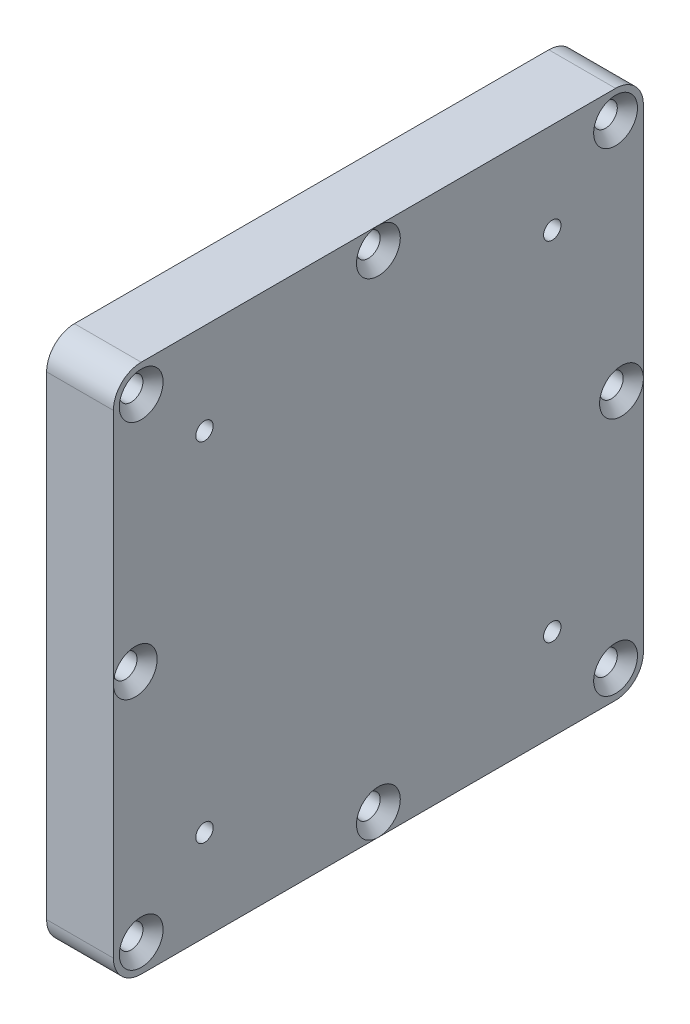
SolidWorks part; units mm, degrees
ref_plane "Front Plane" through (0, 0, 0) normal (0, 0, 1) x (1, 0, 0)
ref_plane "Top Plane" through (0, 0, 0) normal (0, 1, 0) x (1, 0, 0)
ref_plane "Right Plane" through (0, 0, 0) normal (1, 0, 0) x (0, 0, -1)
sketch "Sketch2" plane through (0, 0, 0) normal (1, 0, 0) x (0, 0, -1)
  line L1 (-34.1, -38.1) -> (34.1, -38.1)
  line L2 (-38.1, -34.1) -> (-38.1, 34.1)
  line L3 (-34.1, 38.1) -> (34.1, 38.1)
  line L4 (38.1, -34.1) -> (38.1, 34.1)
  line L5 (-38.1, -38.1) -> (38.1, 38.1) construction
  line L6 (-38.1, 38.1) -> (38.1, -38.1) construction
  arc A0 (-34.1, -38.1) -> (-38.1, -34.1) centre (-34.1, -34.1) cw
  arc A1 (34.1, -38.1) -> (38.1, -34.1) centre (34.1, -34.1) ccw
  arc A2 (34.1, 38.1) -> (38.1, 34.1) centre (34.1, 34.1) cw
  arc A3 (-38.1, 34.1) -> (-34.1, 38.1) centre (-34.1, 34.1) cw
  point P0 (0, 0)
  dimension "D3" = 4
  dimension "D1" = 76.2
  dimension "D2" = 76.2
extrude "Boss-Extrude1" add sketch "Sketch2" along normal blind 9.6
sketch "Sketch21" plane through (9.6, 0, 0) normal (-1, 0, 0) x (0, 0, 1)
  line L0 (-34.1, 34.1) -> (-34.1, -34.1) construction
  line L1 (-34.1, -34.1) -> (34.1, -34.1) construction
  line L2 (-38.1, -34.1) -> (-38.1, 34.1) construction
  line L3 (-34.1, 38.1) -> (34.1, 38.1) construction
  line L4 (38.1, 34.1) -> (38.1, -34.1) construction
  line L5 (34.1, -38.1) -> (-34.1, -38.1) construction
  line L6 (34.1, -34.1) -> (34.1, 34.1) construction
  line L7 (34.1, 34.1) -> (-34.1, 34.1) construction
  dimension "D1" = 4
  dimension "D2" = 4
  dimension "D3" = 4
  dimension "D4" = 4
sketch "Sketch22" plane through (9.6, 0, 0) normal (-1, 0, 0) x (0, 0, 1)
  line L0 (38.1, 34.1) -> (38.1, -34.1) construction
  line L1 (-38.1, -34.1) -> (-38.1, 34.1) construction
  line L3 (34.1, -38.1) -> (-34.1, -38.1) construction
  line L4 (-34.1, 38.1) -> (34.1, 38.1) construction
  point P0 (-34.1, 34.1)
  point P3 (34.1, 34.1)
  point P6 (34.1, -34.1)
  point P9 (-34.1, -34.1)
  point P12 (0, 34.95)
  point P14 (34.95, 0)
  point P16 (0, -34.95)
  point P18 (-34.95, 0)
  point P21 (0, 0)
  point P22 (0, 0)
  point P23 (0, 0)
  point P24 (0, 0)
  point P25 (0, 0)
  point P26 (0, 0)
  point P27 (0, 0)
  point P28 (0, 0)
  point P29 (-0.5366, 33.35)
  point P31 (-33.35, 0)
  point P32 (0, 33.35)
  point P33 (0, -32.4859)
  point P34 (34.3534, 0)
  point P35 (0, 33.35)
  point P47 (0, 0)
  dimension "D1" = 3.15
  dimension "D2" = 3.15
  dimension "D3" = 3.15
  dimension "D4" = 3.15
hole_wizard "CSK for M3 Flat Head Machine Screw1" positions "Sketch22" profile "Sketch23" countersink size "M3" standard "ANSI Metric" end condition through all
sketch "Sketch23" plane through (9.6, 34.1, -34.1) normal (0, 1, 0) x (0, 0, -1)
  line L0 (0, 0) -> (0, 9.6)
  line L1 (0, 9.6) -> (1.7, 9.6)
  line L2 (1.7, 9.6) -> (1.7, 1.45)
  line L3 (1.7, 1.45) -> (3.15, 0)
  line L5 (3.15, 0) -> (0, 0)
  line L6 (-1.7, 1.45) -> (-3.15, 0) construction
  line L11 (0, -6.35) -> (0, 107.95) construction
  dimension "Thru Hole Dia." = 3.4
  dimension "Thru Hole Depth" = 9.6
  dimension "Near C'Sink Dia." = 6.3
  dimension "Near C'Sink Angle" = 90
sketch "Sketch27" plane through (9.6, 0, 0) normal (1, 0, 0) x (0, 0, -1)
  point P0 (-25, 25)
  point P2 (25, 25)
  point P4 (25, -25)
  point P6 (-25, -25)
  point P15 (0, 0)
  point P16 (-25, 21.2401)
  dimension "D1" = 50
  dimension "D2" = 25
  dimension "D3" = 25
  dimension "D4" = 25
hole_wizard "M3x0.5 Tapped Hole1" positions "Sketch27" profile "Sketch26" tap size "M3x0.5" standard "ANSI Metric"
sketch "Sketch26" plane through (9.6, 25, 25) normal (0, 1, 0) x (0, 0, -1)
  line L0 (0, 0) -> (0, 7.5)
  line L1 (0, 7.5) -> (1.25, 6.7489)
  line L2 (1.25, 6.7489) -> (1.25, 0)
  line L5 (1.25, 0) -> (0, 0)
  line L10 (0, 7.5) -> (-1.25, 6.7489) construction
  line L11 (0, -6.35) -> (0, 107.95) construction
  dimension "Tap Drill Dia." = 2.5
  dimension "Tap Drill Depth" = 7.5
  dimension "Drill Angle" = 118
